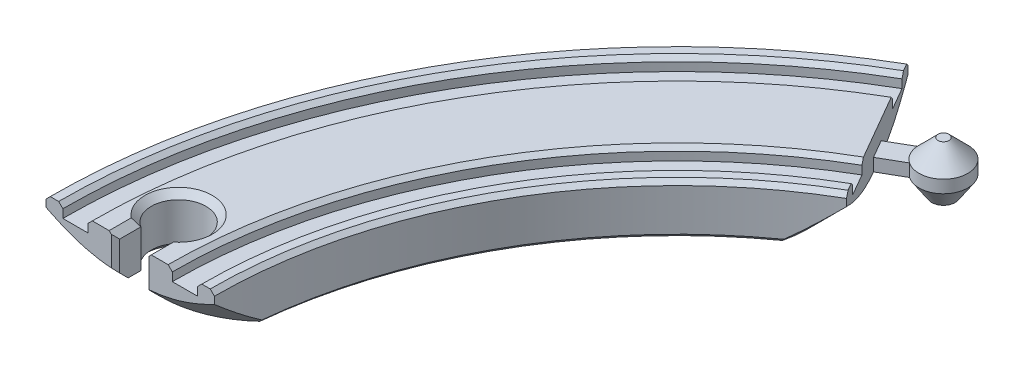
SolidWorks part; units mm, degrees
ref_plane "Front Plane" through (0, 0, 0) normal (0, 0, 1) x (1, 0, 0)
ref_plane "Top Plane" through (0, 0, 0) normal (0, 1, 0) x (1, 0, 0)
ref_plane "Right Plane" through (0, 0, 0) normal (1, 0, 0) x (0, 0, -1)
sketch "Sketch2" plane through (0, 0, 0) normal (0, 0, 1) x (1, 0, 0)
  line L0 (-20, 0) -> (20, 0)
  line L1 (20, 0) -> (20, 12)
  line L2 (20, 12) -> (16, 12)
  line L3 (16, 12) -> (16, 9)
  line L4 (16, 9) -> (10, 9)
  line L5 (10, 9) -> (10, 12)
  line L6 (10, 12) -> (-10, 12)
  line L7 (-10, 12) -> (-10, 9)
  line L8 (-10, 9) -> (-16, 9)
  line L9 (-16, 9) -> (-16, 12)
  line L10 (-16, 12) -> (-20, 12)
  line L11 (-20, 12) -> (-20, 0)
  line L12 (129.9038, 0) -> (129.9038, 12)
  point P4 (0, 0)
  dimension "D1" = 40
  dimension "D2" = 12
  dimension "D3" = 3
  dimension "D4" = 4
  dimension "D5" = 6
  dimension "D6" = 129.9038
revolve "Revolve1" add sketch "Sketch2" angle 60 about L12 region at (0, 5.6351, 0) reverse direction yes
sketch "Sketch3" plane through (0, 12, 0) normal (0, 1, 0) x (1, 0, 0)
  line L0 (10, 0) -> (-10, 0) construction
  line L2 (-3.5, 0) -> (3.5, 0)
  line L3 (-3.5, 0) -> (-3.5, 11.5)
  line L4 (-3.5, 11.5) -> (3.5, 11.5)
  line L5 (3.5, 0) -> (3.5, 11.5)
  line L6 (-3.5, 0) -> (3.5, 11.5) construction
  line L7 (-3.5, 11.5) -> (3.5, 0) construction
  circle A0 centre (0, 11.5) radius 6.5
  point P4 (0, 5.75)
  point P10 (0, 0)
  line M6 (-10, 0) -> (10, 0)
  dimension "D1" = 13
  dimension "D2" = 11.5
  dimension "D3" = 7
extrude "Cut-Extrude1" cut sketch "Sketch3" against normal through all contours L5 A0 L3 L4 | L3 A0 L5 L4 | A0 L3 L5 M6 region at (0, 12, -2.6732) region at (0, 12, -12.9919) region at (0, 12, -8.4074)
sketch "Sketch4" plane through (0, 12, 0) normal (0, 1, 0) x (1, 0, 0)
  line L0 (66.2019, 110.3349) -> (63.7019, 114.6651)
  line L1 (66.2019, 110.3349) -> (76.1612, 116.0849)
  line L2 (63.7019, 114.6651) -> (73.6612, 120.4151)
  line L3 (76.1612, 116.0849) -> (73.6612, 120.4151)
  line L4 (69.9519, 103.8397) -> (59.9519, 121.1603) construction
  circle A0 centre (74.9112, 118.25) radius 5.8
  point P9 (64.9519, 112.5)
  line M6 (69.9519, 103.8397) -> (59.9519, 121.1603)
  dimension "D1" = 11.6
  dimension "D2" = 5
  dimension "D3" = 11.5
extrude "Boss-Extrude1" add sketch "Sketch4" against normal up to surface (12 mm away) contours L1 A0 L2 L3 | L2 A0 L1 L3 region at (72.4777, 12, -116.845) region at (75.7915, 12, -118.7583) up to face at (12.4699, 0, -33.3033)
extrude "Boss-Extrude2" add sketch "Sketch4<3>" against normal blind 7.5 contours A0 L2 L1 M6 region at (67.5022, 12, -113.9724)
sketch "Sketch4<3>" plane through (0, 12, 0) normal (0, 1, 0) x (1, 0, 0) same geometry as "Sketch4"
extrude "Cut-Extrude2" cut sketch "Sketch4<5>" against normal blind 4.5 contours A0 L2 L1 M6 region at (67.5022, 12, -113.9724)
sketch "Sketch4<5>" plane through (0, 12, 0) normal (0, 1, 0) x (1, 0, 0) same geometry as "Sketch4"
chamfer "Chamfer2" distance 4.5 angle 45 1 edges at (69.1112, 12, -118.25)
chamfer "Chamfer5" distance 3 distance2 4.5 1 edges at (74.9112, 0, -124.05) first distance on face at (74.9112, 0, -124.05)
chamfer "Chamfer3" distance 1.5 angle 45 6 edges at (0, 0, -18) (0, 12, -18) (3.5, 0, -3.0114) (-3.5, 0, -3.0114) (3.5, 12, -3.0114) (-3.5, 12, -3.0114)
sketch "Sketch17" plane through (-33.726, 0, -58.4151) normal (-0.5, 0, -0.866) x (-0.866, 0, 0.5)
  line L0 (-118.7665, 10.7665) -> (-118.7665, 0)
  line L1 (-118.7665, 0) -> (-108, 0)
  line L2 (-108, 0) -> (-118.7665, 10.7665)
  line L4 (-83, -1.2652) -> (-83, 10.7665) construction
  dimension "D1" = 25
revolve "Cut-Revolve1" cut sketch "Sketch17" angle 90 about L4
ref_plane "Plane1" through (-32.476, 0, -56.25) normal (-0.5, 0, -0.866) x (-0.866, 0, 0.5)
mirror "Mirror1" about plane through (-32.476, 0, -56.25) normal (-0.5, 0, -0.866) of "Cut-Revolve1"
chamfer "Chamfer4" distance 4.5 angle 45 1 edges at (64.9519, 0, -112.5)
ref_plane "Plane2" through (32.476, 0, -56.25) normal (0.5, 0, -0.866) x (-0.866, 0, -0.5)
mirror "Mirror4" about plane through (32.476, 0, -56.25) normal (0.5, 0, -0.866) of "Cut-Revolve1", "Mirror1"
chamfer "Chamfer1" distance 1 angle 45 10 edges at (34.7243, 12, -54.9519) (31.2602, 12, -56.9519) (26.0641, 12, -59.9519) (8.7436, 12, -69.9519) (3.5474, 12, -72.9519) (0.0833, 12, -74.9519) (34.7243, 0, -54.9519) (0.0833, 0, -74.9519) (3.5, 7.5085, 0) (-3.5, 7.5085, 0)
